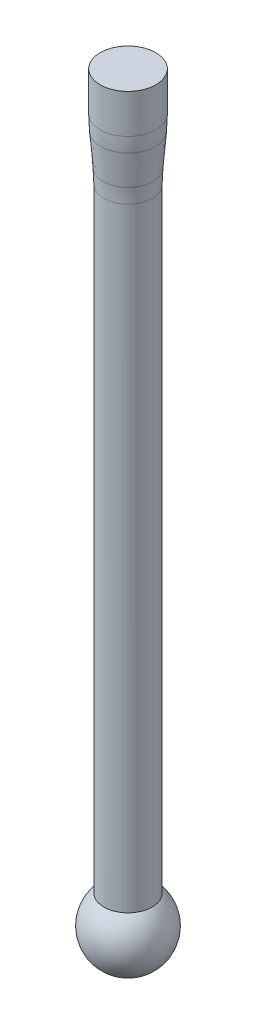
SolidWorks part; units mm, degrees
ref_plane "Front Plane" through (0, 0, 0) normal (0, 0, 1) x (1, 0, 0)
ref_plane "Top Plane" through (0, 0, 0) normal (0, 1, 0) x (1, 0, 0)
ref_plane "Right Plane" through (0, 0, 0) normal (1, 0, 0) x (0, 0, -1)
sketch "Sketch1" plane through (0, 0, 0) normal (0, 0, 1) x (1, 0, 0)
  line L0 (0, -119.7701) -> (0, 5868.733) construction
  line L1 (0, 0) -> (1.5, 0)
  line L2 (1.5, 0) -> (1.5, -2.5)
  line L4 (1.3, -5) -> (1.3, -38.4801)
  line L5 (0, -42) -> (0, 0)
  line L6 (1.3, -5) -> (1.5, -2.5)
  arc A0 (0, -42) -> (1.3, -38.4801) centre (0, -40) ccw
  dimension "D1" = 4
  dimension "D2" = 0.2
  dimension "D3" = 40
  dimension "D4" = 2.5
  dimension "D5" = 3
  dimension "D6" = 2.5
revolve "Revolve1" add sketch "Sketch1" angle 360 about L0
fillet "Fillet1" radius 10 2 edges at (1.3, -5, 0) (1.5, -2.5, 0)
